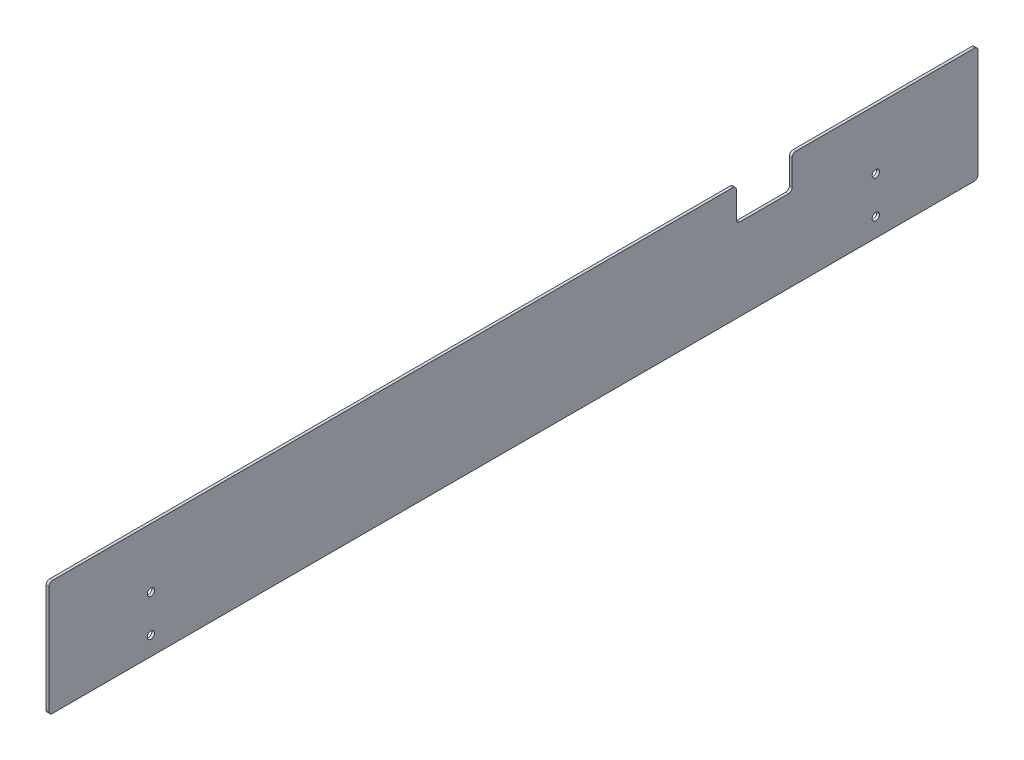
SolidWorks part; units mm, degrees
ref_plane "Front Plane" through (0, 0, 0) normal (0, 0, 1) x (1, 0, 0)
ref_plane "Top Plane" through (0, 0, 0) normal (0, 1, 0) x (1, 0, 0)
ref_plane "Right Plane" through (0, 0, 0) normal (1, 0, 0) x (0, 0, -1)
sketch "Sketch1" plane through (0, 0, 0) normal (1, 0, 0) x (0, 0, -1)
  line L0 (130.0532, -78.2926) -> (230.0532, -78.2926)
  line L1 (-269.9468, -78.2926) -> (100.0532, -78.2926)
  line L2 (-269.9468, -78.2926) -> (-269.9468, -140.2926)
  line L3 (-269.9468, -140.2926) -> (230.0532, -140.2926)
  line L4 (230.0532, -78.2926) -> (230.0532, -140.2926)
  line L6 (130.0532, -78.2926) -> (130.0532, -96.1491)
  line L7 (130.0532, -96.1491) -> (100.0532, -96.1491)
  line L8 (100.0532, -78.2926) -> (100.0532, -96.1491)
  dimension "D1" = 500
  dimension "D2" = 62
  dimension "D3" = 30
  dimension "D4" = 100
extrude "Boss-Extrude1" add sketch "Sketch1" along normal blind 1.5
fillet "Fillet1" radius 2 8 edges at (0.75, -140.2926, -230.0532) (0.75, -140.2926, 269.9468) (0.75, -78.2926, 269.9468) (0.75, -78.2926, -100.0532) (0.75, -96.1491, -100.0532) (0.75, -96.1491, -130.0532) (0.75, -78.2926, -130.0532) (0.75, -78.2926, -230.0532)
sketch "Sketch2" plane through (0, 0, 0) normal (-1, 0, 0) x (0, 0, 1)
  line L0 (-230.0532, -138.2926) -> (-230.0532, -80.2926) construction
  line L1 (267.9468, -140.2926) -> (-228.0532, -140.2926) construction
  line L2 (269.9468, -80.2926) -> (269.9468, -138.2926) construction
  circle A0 centre (-175.0532, -110.2926) radius 1.95
  circle A1 centre (-175.0532, -130.2926) radius 1.95
  circle A2 centre (214.9468, -110.2926) radius 1.95
  circle A3 centre (214.9468, -130.2926) radius 1.95
  point P10 (0, 0)
  point P12 (-171.69, -139.1289)
  point P16 (0, 0)
  point P17 (0, 0)
  dimension "D1" = 55
  dimension "D2" = 20
  dimension "D3" = 10
  dimension "D4" = 55
  dimension "D5" = 20
  dimension "D6" = 10
extrude "Cut-Extrude1" cut sketch "Sketch2" against normal blind 10
